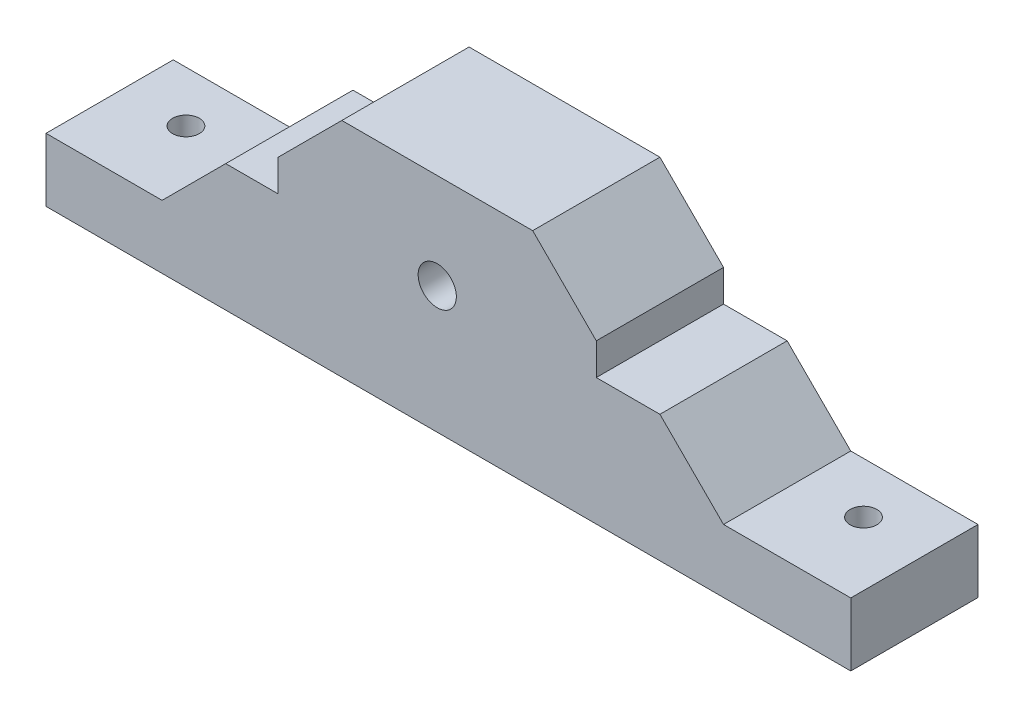
SolidWorks part; units mm, degrees
ref_plane "Спереди" through (0, 0, 0) normal (0, 0, 1) x (1, 0, 0)
ref_plane "Сверху" through (0, 0, 0) normal (0, 1, 0) x (1, 0, 0)
ref_plane "Справа" through (0, 0, 0) normal (1, 0, 0) x (0, 0, -1)
ref_plane "Плоскость4" through (0, 254.196, 0) normal (0, 1, 0) x (1, 0, 0)
sketch "Эскиз1" plane through (0, 254.196, 0) normal (0, 1, 0) x (1, 0, 0)
  line L0 (1.559, -32.2731) -> (1.559, -52.2731)
  line L1 (1.559, 34.1) -> (1.559, -34.1) construction
  line L2 (1.559, -52.2731) -> (128.059, -52.2731)
  line L3 (128.059, -60.5) -> (128.059, 60.5) construction
  line L4 (128.059, -34.1) -> (128.059, 34.1) construction
  line L5 (128.059, -52.2731) -> (128.059, -32.2731)
  line L6 (128.059, -32.2731) -> (1.559, -32.2731)
  circle A0 centre (11.559, -40.2731) radius 2.1
  circle A1 centre (118.059, -40.2731) radius 2.1
extrude "Бобышка-Вытянуть1" add sketch "Эскиз1" along normal blind 40
ref_plane "Плоскость5" through (0, 0, 32.2731) normal (0, 0, -1) x (-1, 0, 0)
sketch "Эскиз2" plane through (0, 0, 32.2731) normal (0, 0, -1) x (-1, 0, 0)
  line L0 (-128.059, 294.196) -> (-128.059, 274.196)
  line L4 (-128.059, 294.196) -> (-128.059, 254.196) construction
  line L6 (-88.059, 274.146) -> (-88.059, 289.146)
  line L7 (-88.059, 289.146) -> (-38.059, 289.146)
  line L8 (-38.059, 289.146) -> (-38.059, 274.146)
  line L10 (-1.559, 294.196) -> (-1.559, 254.196) construction
  line L11 (-1.559, 274.196) -> (-1.559, 294.196)
  line L12 (-1.559, 294.196) -> (-128.059, 294.196)
  line L14 (-108.059, 274.146) -> (-108.059, 264.146)
  line L15 (-108.059, 264.146) -> (-128.059, 264.146)
  line L16 (-128.059, 264.146) -> (-128.059, 274.196)
  line L17 (-108.059, 274.146) -> (-88.059, 274.146)
  line L18 (-1.559, 274.196) -> (-1.559, 264.146)
  line L19 (-1.559, 264.146) -> (-19.809, 264.146)
  line L20 (-19.809, 264.146) -> (-19.809, 274.146)
  line L21 (-19.809, 274.146) -> (-38.059, 274.146)
  circle A0 centre (-63.059, 274.146) radius 3
extrude "Вырез-Вытянуть1" cut sketch "Эскиз2" against normal through all
chamfer "Фаска1" distance 10 angle 45 2 edges at (38.059, 289.146, 42.2731) (88.059, 289.146, 42.2731)
chamfer "Фаска2" distance 10 angle 45 2 edges at (19.809, 274.146, 42.2731) (108.059, 274.146, 42.2731)
